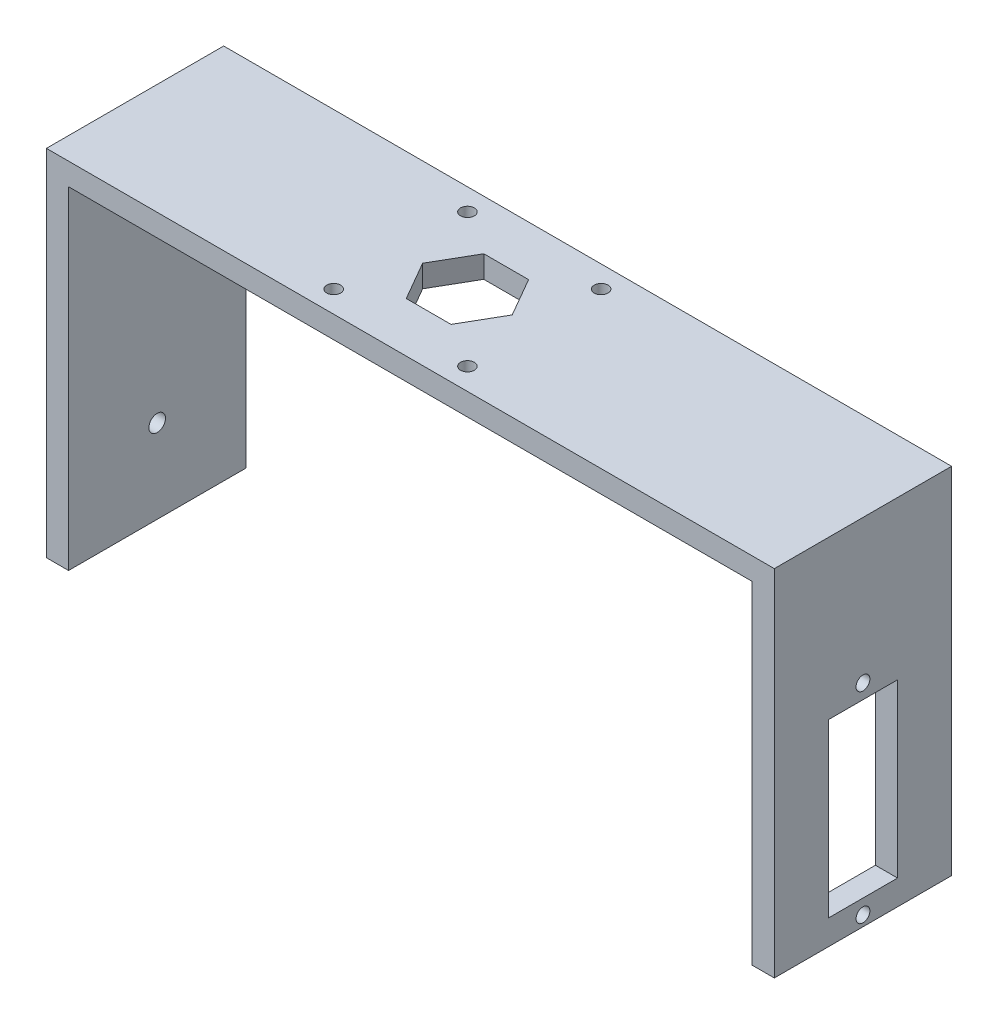
SolidWorks part; units mm, degrees
ref_plane "Front Plane" through (0, 0, 0) normal (0, 0, 1) x (1, 0, 0)
ref_plane "Top Plane" through (0, 0, 0) normal (0, 1, 0) x (1, 0, 0)
ref_plane "Right Plane" through (0, 0, 0) normal (1, 0, 0) x (0, 0, -1)
sketch "Sketch1" plane through (0, 0, 0) normal (0, 0, 1) x (1, 0, 0)
  line L0 (-56, 0) -> (-56, 60)
  line L1 (-56, 60) -> (67.4, 60)
  line L2 (71.4, 0) -> (67.4, 0)
  line L3 (71.4, 64) -> (-60, 64)
  line L4 (-60, 64) -> (-60, 0)
  line L5 (-60, 0) -> (-56, 0)
  line L6 (-56, 0) -> (0, 0) construction
  line L7 (0, 0) -> (0, 47) construction
  line L8 (71.4, 64) -> (71.4, 0)
  line L9 (67.4, 0) -> (67.4, 60)
  line L10 (56, 60) -> (56, 0) construction
  dimension "D1" = 4
  dimension "D2" = 4
  dimension "D3" = 56
  dimension "D4" = 60
  dimension "D5" = 56
  dimension "D6" = 11.4
extrude "Boss-Extrude1" add sketch "Sketch1" along normal mid plane 32
sketch "Sketch5" plane through (71.4, 0, 0) normal (1, 0, 0) x (0, 0, -1)
  line L0 (6.25, 35.5) -> (-6.25, 4.5) construction
  line L1 (5.875, 34.85) -> (-5.875, 34.85) construction
  line L2 (5.875, 34.85) -> (5.875, 5.15) construction
  line L3 (5.875, 5.15) -> (-5.875, 5.15) construction
  line L4 (-5.875, 34.85) -> (-5.875, 5.15) construction
  line L5 (6.25, 4.5) -> (-6.25, 4.5)
  line L6 (6.25, 4.5) -> (6.25, 35.5)
  line L7 (6.25, 35.5) -> (-6.25, 35.5)
  line L8 (-6.25, 4.5) -> (-6.25, 35.5)
  line L9 (5.875, 5.15) -> (-5.875, 34.85) construction
  line L10 (0, 20) -> (0, 0) construction
  line L11 (-16, 0) -> (16, 0) construction
  line L12 (0, 20) -> (3.7688, 20) construction
  circle A1 centre (0, 1.875) radius 1.25
  circle A2 centre (0, 38.125) radius 1.25
  circle A4 centre (0, 15.075) radius 1.5
  dimension "D6" = 36.25
  dimension "D7" = 2.5
  dimension "D9" = 13.2
  dimension "D10" = 3
  dimension "D1" = 11.75
  dimension "D2" = 29.7
  dimension "D3" = 12.5
  dimension "D4" = 31
  dimension "D5" = 20
extrude "Cut-Extrude2" cut sketch "Sketch5" against normal up to next contours L6 L7 L8 L5 | A2 | A1
extrude "Cut-Extrude3" cut sketch "Sketch5<3>" against normal through all contours A4
sketch "Sketch5<3>" plane through (71.4, 0, 0) normal (1, 0, 0) x (0, 0, -1) same geometry as "Sketch5"
sketch "Sketch3" plane through (0, 64, 0) normal (0, 1, 0) x (1, 0, 0)
  line L1 (4.0415, -7) -> (8.0829, 0)
  line L2 (8.0829, 0) -> (4.0415, 7)
  line L3 (4.0415, 7) -> (-4.0415, 7)
  line L4 (-4.0415, 7) -> (-8.0829, 0)
  line L5 (-8.0829, 0) -> (-4.0415, -7)
  line L6 (-4.0415, -7) -> (4.0415, -7)
  circle A0 centre (0, 0) radius 7 construction
  circle A1 centre (-12.0703, 12.0703) radius 1.25
  circle A2 centre (12.0703, 12.0703) radius 1.25
  circle A3 centre (12.0703, -12.0703) radius 1.25
  circle A4 centre (-12.0703, -12.0703) radius 1.25
  point P20 (0, 0)
  dimension "D1" = 14
  dimension "D3" = 2.5
  dimension "D4" = 34.14
  dimension "D2" = 4
extrude "Cut-Extrude1" cut sketch "Sketch3" against normal up to next
